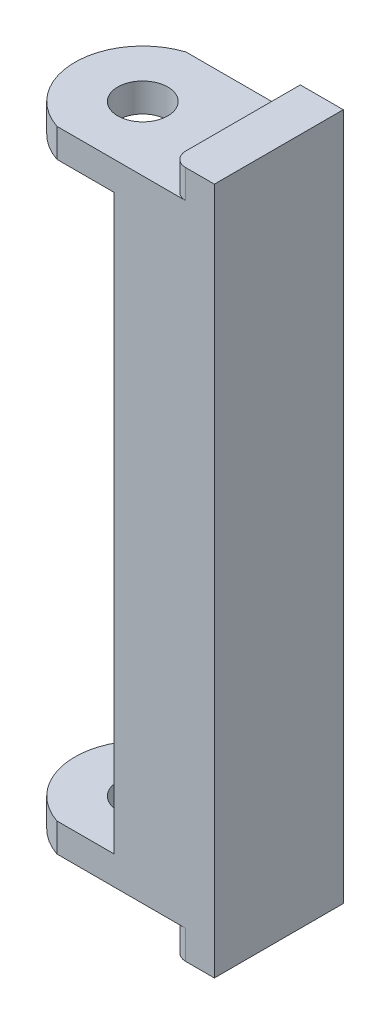
SolidWorks part; units mm, degrees
ref_plane "Front Plane" through (0, 0, 0) normal (0, 0, 1) x (1, 0, 0)
ref_plane "Top Plane" through (0, 0, 0) normal (0, 1, 0) x (1, 0, 0)
ref_plane "Right Plane" through (0, 0, 0) normal (1, 0, 0) x (0, 0, -1)
sketch "Sketch1" plane through (0, 0, 0) normal (0, 1, 0) x (1, 0, 0)
  line L0 (-2.5, 0) -> (2.5, 0) construction
  line L5 (-3.991, 4.5) -> (4, 4.5)
  line L6 (-3.991, -4.5) -> (4, -4.5)
  line L8 (7, -4.5) -> (7, 4.5)
  line L10 (5.0195, 4.5) -> (4, 4.5)
  line L11 (7, -4.5) -> (5, -4.5)
  line L12 (7, -4.5) -> (7, 4.5)
  line L13 (7, 4.5) -> (5.0195, 4.5)
  line L14 (4, -3.5) -> (4, 4.5)
  line L15 (5, -4.5) -> (4, -4.5)
  arc A1 (-3.991, 4.5) -> (-3.991, -4.5) centre (-2.5, 0) ccw
  circle A3 centre (-2.5, 0) radius 1.75
  arc A4 (0.0045, 4.5) -> (0.0045, -4.5) centre (-2.5, 0) cw
  arc A6 (5, -4.5) -> (4, -3.5) centre (5, -3.5) cw
  point P2 (0, 0)
  dimension "D2" = 9.5
  dimension "D3" = 3.5
  dimension "D6" = 5.15
  dimension "D8" = 1
  dimension "D1" = 9
  dimension "D4" = 5
  dimension "D5" = 2.5
  dimension "D7" = 3
extrude "Boss-Extrude3" add sketch "Sketch1" along normal blind 2 contours A4 L5 A1 L6 A3 | L5 A4 L6 | L12 L13 L10 L14 A6 L11 region at (-1.9933, 0, -4.3663) region at (2.8287, 0, 0.0477)
extrude "Boss-Extrude4" add sketch "Sketch1<3>" against normal blind 20 contours L5 A4 L6 | L12 L13 L10 L14 A6 L11 region at (2.8287, 0, 0.0477)
sketch "Sketch1<3>" plane through (0, 0, 0) normal (0, 1, 0) x (1, 0, 0) same geometry as "Sketch1"
extrude "Boss-Extrude5" add sketch "Sketch1<5>" along normal blind 4 contours L13 L14 L11 L8 region at (5.5102, 0, -0.0343)
sketch "Sketch1<5>" plane through (0, 0, 0) normal (0, 1, 0) x (1, 0, 0) same geometry as "Sketch1"
mirror "Mirror1" about plane through (0, -20, 0) normal (0, 1, 0) of bodies 111
